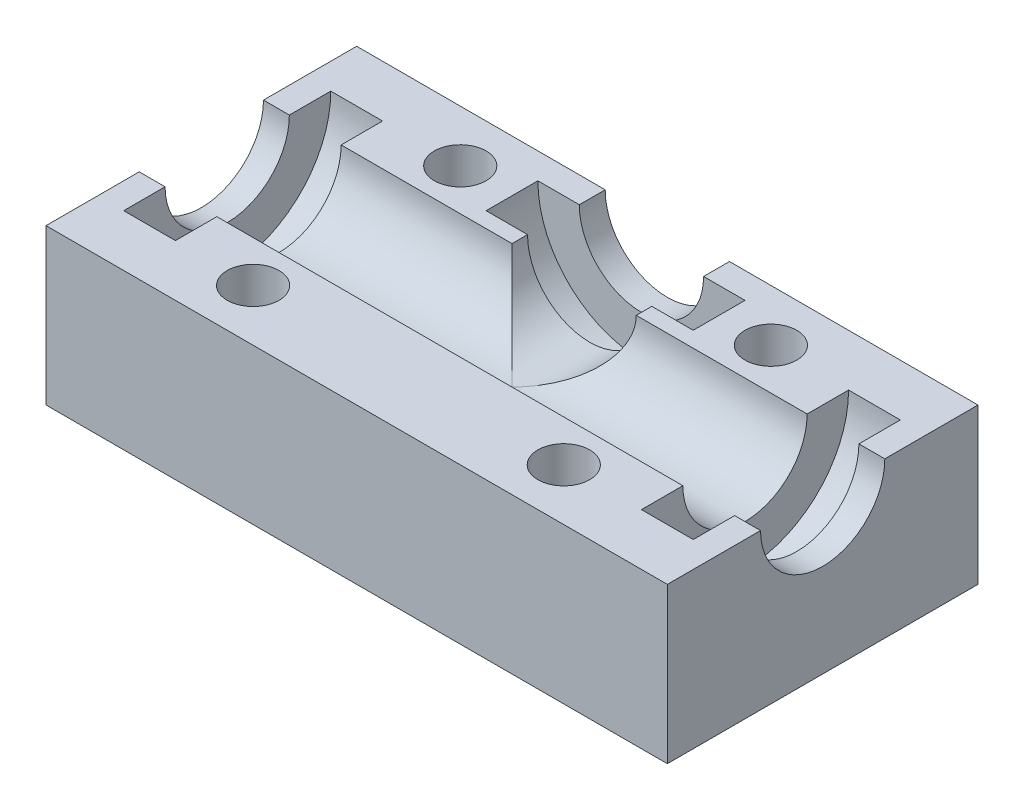
SolidWorks part; units mm, degrees
ref_plane "Front Plane" through (0, 0, 0) normal (0, 0, 1) x (1, 0, 0)
ref_plane "Top Plane" through (0, 0, 0) normal (0, 1, 0) x (1, 0, 0)
ref_plane "Right Plane" through (0, 0, 0) normal (1, 0, 0) x (0, 0, -1)
sketch "Sketch1" plane through (0, 0, 0) normal (0, 1, 0) x (1, 0, 0)
  line L0 (0, 15) -> (60, 15) construction
  line L1 (0, 30) -> (60, 30)
  line L2 (0, 30) -> (0, 0)
  line L3 (0, 0) -> (60, 0)
  line L4 (60, 30) -> (60, 0)
  line L5 (30, 30) -> (30, 0) construction
  line L6 (45, 25) -> (60, 25) construction
  line L7 (45, 25) -> (45, 30) construction
  circle A0 centre (45, 25) radius 2.5
  circle A1 centre (45, 5) radius 2.5
  circle A2 centre (15, 5) radius 2.5
  circle A3 centre (15, 25) radius 2.5
  dimension "D3" = 5
  dimension "D1" = 60
  dimension "D2" = 30
  dimension "D4" = 15
  dimension "D5" = 5
extrude "Boss-Extrude1" add sketch "Sketch1" along normal blind 30
sketch "Sketch2" plane through (0, 0, 0) normal (-1, 0, 0) x (0, 0, 1)
  line L0 (-15, 30) -> (-15, 0) construction
  line L1 (-30, 30) -> (0, 30) construction
  line L2 (-30, 0) -> (0, 0) construction
  line L3 (-30, 15) -> (0, 15) construction
  line L4 (-30, 30) -> (-30, 0) construction
  line L5 (0, 30) -> (0, 0) construction
  circle A0 centre (-15, 15) radius 6
  circle A1 centre (-15, 15) radius 10
  dimension "D1" = 12
  dimension "D2" = 20
extrude "Cut-Extrude1" cut sketch "Sketch2" against normal through all contours A0
extrude "Cut-Extrude2" cut sketch "Sketch2<4>" against normal blind 5 from offset 2.5 offset against normal yes
sketch "Sketch2<4>" plane through (0, 0, 0) normal (-1, 0, 0) x (0, 0, 1) same geometry as "Sketch2"
ref_plane "Plane1" through (30, 0, 0) normal (-1, 0, 0) x (0, 0, 1)
mirror "Mirror1" about plane through (30, 0, 0) normal (-1, 0, 0) of "Cut-Extrude2"
sketch "Sketch6" plane through (0, 0, -30) normal (0, 0, -1) x (-1, 0, 0)
  line L0 (-60, 30) -> (0, 0) construction
  line L1 (-60, 0) -> (0, 30) construction
  circle A0 centre (-30, 15) radius 6
  circle A1 centre (-30, 15) radius 10
  dimension "D1" = 12
  dimension "D2" = 20
extrude "Cut-Extrude5" cut sketch "Sketch6" against normal blind 15 contours A0
ref_plane "Plane2" through (0, 15, 0) normal (0, -1, 0) x (-1, 0, 0)
extrude "Cut-Extrude6" cut sketch "Sketch6<3>" against normal blind 5 from offset 2.5 contours A0 | A1 A0 region at (30, 15, -30) region at (39.7172, 15, -30) offset against normal yes
sketch "Sketch6<3>" plane through (0, 0, -30) normal (0, 0, -1) x (-1, 0, 0) same geometry as "Sketch6"
split "Split2" trim tools "Plane2" bodies to split 109 resulting bodies 112 113
delete or keep bodies "Body-Delete/Keep 1" type delete bodies bodies 112
equation "\"WIDTH_CENTRE\"= 0.06m"
equation "\"LENGTH_CENTRE\"= 0.03m"
equation "\"D1@Sketch1\"=\"WIDTH_CENTRE\""
equation "\"D2@Sketch1\"=\"LENGTH_CENTRE\""
equation "\"HEIGHT_CENTRE\"=0.03"
equation "\"D1@Boss-Extrude1\"=\"HEIGHT_CENTRE\""
equation "\"SIDE_SHAFT_DIAM\"= 12mm"
equation "\"D1@Sketch2\"=\"SIDE_SHAFT_DIAM\""
equation "\"OUTER_DIAM_SIDE_BEARINGS\"= 0.02"
equation "\"D2@Sketch2\"=\"OUTER_DIAM_SIDE_BEARINGS\""
equation "\"SIDE_BEARING_WIDTH\"= 0.005"
equation "\"D1@Cut-Extrude2\"= \"SIDE_BEARING_WIDTH\""
equation "\"SIDE_INSERT_EDGE\"=0.003"
equation "\"SIDE_INSERT_DIAM\"= 0.003"
equation "\"SIDE_INSERT_DEPTH\"=0.01"
equation "\"CENTRE_SHAFT_DIAM\"= 12mm"
equation "\"D1@Sketch6\"= \"CENTRE_SHAFT_DIAM\""
equation "\"OUTER_DIAM_CENTRE_BEARINGS\"= 0.02m"
equation "\"D2@Sketch6\"=\"OUTER_DIAM_CENTRE_BEARINGS\""
equation "\"D1@Cut-Extrude5\"=\"LENGTH_CENTRE\"*0.5"
equation "\"SIDE_BEARING_LIP_DEPTH\"= 0.0025"
equation "\"D19@Cut-Extrude2\"=\"SIDE_BEARING_LIP_DEPTH\""
equation "\"CENTRE_BEARING_LIP_DEPTH\"= 0.0025"
equation "\"D19@Cut-Extrude6\"=\"CENTRE_BEARING_LIP_DEPTH\""
equation "\"CENTRE_BEARING_WIDTH\"= 0.005"
equation "\"D1@Cut-Extrude6\"=\"CENTRE_BEARING_WIDTH\""
equation "\"FASTENER_HOLE_OFFSET_X\"= 0.015"
equation "\"D4@Sketch1\"=\"FASTENER_HOLE_OFFSET_X\""
equation "\"FASTENER_DIAM\"= 0.005"
equation "\"D3@Sketch1\"=\"FASTENER_DIAM\""
equation "\"FASTENER_HOLE_OFFSET_Z\"= 0.005"
equation "\"D5@Sketch1\"=\"FASTENER_HOLE_OFFSET_Z\""
